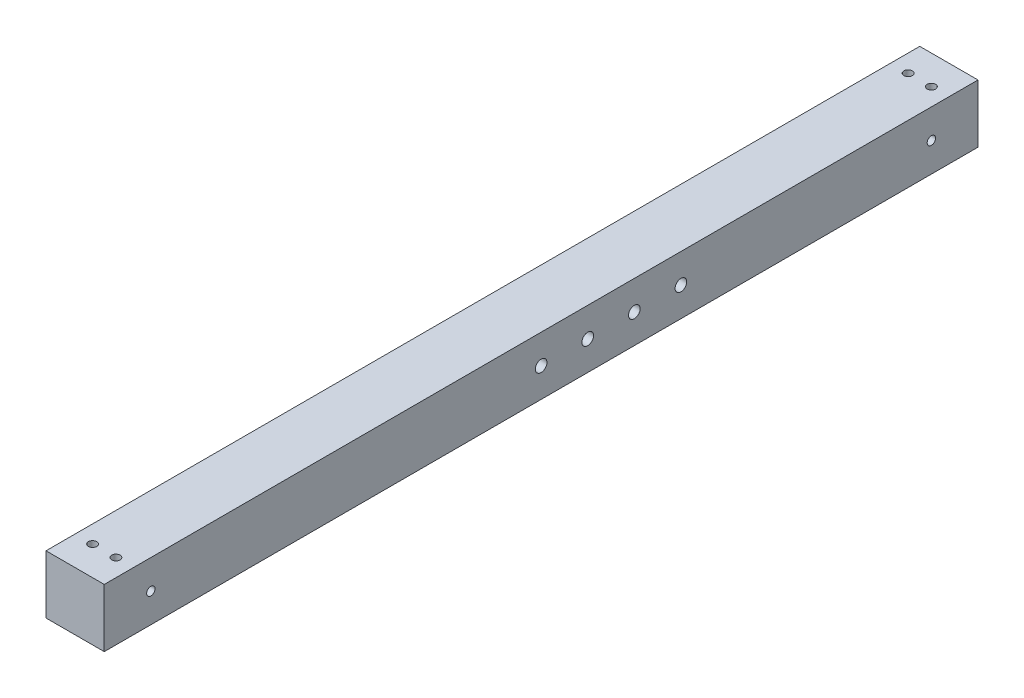
SolidWorks part; units mm, degrees
ref_plane "Front Plane" through (0, 0, 0) normal (0, 0, 1) x (1, 0, 0)
ref_plane "Top Plane" through (0, 0, 0) normal (0, 1, 0) x (1, 0, 0)
ref_plane "Right Plane" through (0, 0, 0) normal (1, 0, 0) x (0, 0, -1)
sketch "Sketch1" plane through (0, 0, 0) normal (0, 0, 1) x (1, 0, 0)
  line L1 (-12.5, 12.5) -> (12.5, 12.5)
  line L2 (-12.5, 12.5) -> (-12.5, -12.5)
  line L3 (-12.5, -12.5) -> (12.5, -12.5)
  line L4 (12.5, 12.5) -> (12.5, -12.5)
  line L5 (-12.5, 12.5) -> (12.5, -12.5) construction
  line L6 (-12.5, -12.5) -> (12.5, 12.5) construction
  point P0 (0, 0)
  dimension "D1" = 25
  dimension "D2" = 25
extrude "Boss-Extrude1" add sketch "Sketch1" along normal blind 200
sketch "Sketch2" plane through (12.5, 0, 0) normal (1, 0, 0) x (0, 0, -1)
  line L0 (-200, -12.5) -> (0, -12.5) construction
  line L1 (0, 12.5) -> (-25, 12.5) construction
  line L2 (0, 12.5) -> (0, -12.5) construction
  line L3 (0, -12.5) -> (-25, -12.5) construction
  line L4 (-25, 12.5) -> (-25, -12.5) construction
  line L5 (0, 12.5) -> (-25, -12.5) construction
  line L6 (0, -12.5) -> (-25, 12.5) construction
  line L7 (0, -12.5) -> (0, 12.5) construction
  circle A0 centre (-12.5, 0) radius 2.5
  point P0 (-12.5, 0)
  dimension "D1" = 25
extrude "Cut-Extrude1" cut sketch "Sketch2" against normal through all
sketch "Sketch3" plane through (0, 12.5, 0) normal (0, 1, 0) x (1, 0, 0)
  line L0 (12.5, -200) -> (-12.5, -200) construction
  line L2 (0, -1000) -> (0, 49000) construction
  circle A0 centre (-5, -187.5) radius 1.8
  circle A1 centre (5, -187.5) radius 1.8
  dimension "D1" = 3.6
  dimension "D2" = 3.6
  dimension "D3" = 12.5
  dimension "D4" = 5
  dimension "D5" = 5
extrude "Cut-Extrude2" cut sketch "Sketch3" against normal through all
sketch "Sketch4" plane through (-12.5, 0, 0) normal (-1, 0, 0) x (0, 0, 1)
  line L0 (200, -12.5) -> (0, -12.5) construction
  line L2 (200, 12.5) -> (200, -12.5) construction
  circle A0 centre (180, 0) radius 1.8
  dimension "D1" = 3.6
  dimension "D3" = 20
  dimension "D2" = 12.5
extrude "Cut-Extrude3" cut sketch "Sketch4" against normal through all both and the other way through all
ref_plane "Plane1" through (0, 0, 12.5) normal (0, 0, -1) x (-1, 0, 0)
mirror "Mirror2" about plane through (0, 0, 12.5) normal (0, 0, -1) of "Cut-Extrude3", "Cut-Extrude2", "Cut-Extrude1", "Boss-Extrude1"
sketch "Sketch6" plane through (12.5, 0, 0) normal (1, 0, 0) x (0, 0, -1)
  line L0 (175, -12.5) -> (175, 12.5) construction
  line L1 (-12.5, -1000) -> (-12.5, 49000) construction
  line L2 (-12.5, 0) -> (7.5, 0) construction
  circle A0 centre (155, 0) radius 1.8 construction
  circle A1 centre (7.5, 0) radius 2.5
  circle A4 centre (-12.5, 0) radius 2.5 construction
  circle A5 centre (-12.5, 0) radius 2.5
  circle A6 centre (27.5, 0) radius 2.5
  circle A7 centre (47.5, 0) radius 2.5
  dimension "D1" = 20
  dimension "D5" = 20
  dimension "D4" = 4
extrude "Cut-Extrude5" cut sketch "Sketch6" against normal through all both and the other way through all
sketch "Sketch7" plane through (-12.5, 0, 0) normal (-1, 0, 0) x (0, 0, 1)
  circle A0 centre (-47.5, 0) radius 3.5
  circle A1 centre (-27.5, 0) radius 3.5
  circle A2 centre (-7.5, 0) radius 3.5
  circle A3 centre (12.5, 0) radius 3.5
  dimension "D1" = 7
  dimension "D2" = 4
